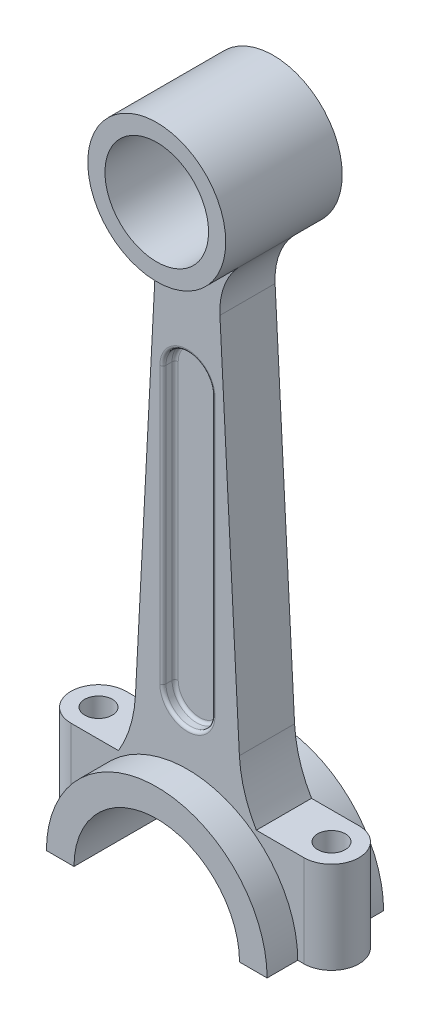
SolidWorks part; units mm, degrees
ref_plane "Front Plane" through (0, 0, 0) normal (0, 0, 1) x (1, 0, 0)
ref_plane "Top Plane" through (0, 0, 0) normal (0, 1, 0) x (1, 0, 0)
ref_plane "Right Plane" through (0, 0, 0) normal (1, 0, 0) x (0, 0, -1)
sketch "Sketch1" plane through (0, 0, 0) normal (0, 0, 1) x (1, 0, 0)
  line L0 (0, 0) -> (0, -201.2) construction
  line L1 (-10, -20.1556) -> (-17.8497, -169.9368)
  line L2 (10, -20.1556) -> (17.8497, -169.9368)
  line L3 (-36, -201.2) -> (36, -201.2) construction
  line L4 (-36, -201.2) -> (-27, -201.2)
  line L5 (27, -201.2) -> (36, -201.2)
  circle A0 centre (0, 0) radius 22.5
  circle A1 centre (0, 0) radius 16.9
  arc A2 (36, -201.2) -> (-36, -201.2) centre (0, -201.2) ccw
  arc A3 (27, -201.2) -> (-27, -201.2) centre (0, -201.2) ccw
  dimension "D1" = 45
  dimension "D2" = 33.8
  dimension "D3" = 72
  dimension "D4" = 54
  dimension "D5" = 201.2
  dimension "D6" = 20
  dimension "D7" = 6
extrude "Boss-Extrude1" add sketch "Sketch1" along normal mid plane 38 contours A1 A0 | A2 A3 region at (-11.5231, 18.5805, 0) region at (0, -166.005, 0)
extrude "Boss-Extrude2" add sketch "Sketch1<3>" along normal mid plane 18 contours L0 A0 L1 A2 | A0 L0 A2 L2 region at (7.1843, -100.8455, 0) region at (-7.1843, -100.8455, 0)
sketch "Sketch1<3>" plane through (0, 0, 0) normal (0, 0, 1) x (1, 0, 0) same geometry as "Sketch1"
sketch "Sketch2" plane through (0, 0, 9) normal (0, 0, 1) x (1, 0, 0)
  line L0 (0, 0) -> (0, -201.2) construction
  line L1 (0, -145.6) -> (0, -55.6) construction
  line L2 (-8, -145.6) -> (-8, -55.6)
  line L3 (8, -145.6) -> (8, -55.6)
  arc A0 (-8, -145.6) -> (8, -145.6) centre (0, -145.6) ccw
  arc A1 (8, -55.6) -> (-8, -55.6) centre (0, -55.6) ccw
  point P6 (0, -100.6)
  dimension "D2" = 8
  dimension "D1" = 90
extrude "Cut-Extrude1" cut sketch "Sketch2" against normal blind 4 contours A1 L2 A0 L3
mirror "Mirror1" about plane through (0, 0, 0) normal (0, 0, 1) of "Cut-Extrude1"
fillet "Fillet1" radius 1 16 edges at (0, -153.6, -5) (8, -100.6, -5) (0, -47.6, -5) (0, -153.6, -9) (8, -100.6, -9) (0, -47.6, -9) (0, -153.6, 5) (8, -100.6, 5) (0, -47.6, 5) (0, -153.6, 9) (8, -100.6, 9) (0, -47.6, 9) (-8, -100.6, -5) (-8, -100.6, -9) (-8, -100.6, 5) (-8, -100.6, 9)
fillet "Fillet2" radius 40 2 edges at (-17.8497, -169.9368, 0) (17.8497, -169.9368, 0)
fillet "Fillet3" radius 22.5 2 edges at (10, -20.1556, 0) (-10, -20.1556, 0)
ref_plane "Plane1" through (0, -171.2, 0) normal (0, -1, 0) x (-1, 0, 0)
sketch "Sketch3" plane through (0, -171.2, 0) normal (0, -1, 0) x (-1, 0, 0)
  line L0 (38, 0) -> (-38, 0) construction
  line L1 (38, -9) -> (-38, -9)
  line L2 (38, 9) -> (-38, 9)
  arc A0 (38, -9) -> (38, 9) centre (38, 0) ccw
  arc A1 (-38, 9) -> (-38, -9) centre (-38, 0) ccw
  point P2 (0, 0)
  dimension "D2" = 9
  dimension "D1" = 76
extrude "Boss-Extrude5" add sketch "Sketch3" along normal up to surface (30 mm away) contours A1 L1 A0 L2 up to face at (31.5, -201.2, 0)
sketch "Sketch6" plane through (0, 0, -9) normal (0, 0, -1) x (-1, 0, 0)
  line L0 (-27, -201.2) -> (27, -201.2) construction
  circle A0 centre (0, -201.2) radius 27
extrude "Cut-Extrude2" cut sketch "Sketch6" against normal blind 37
sketch "Sketch7" plane through (0, -171.2, 0) normal (0, -1, 0) x (-1, 0, 0)
  circle A0 centre (-38, 0) radius 4.5
  circle A1 centre (38, 0) radius 4.5
  dimension "D1" = 9
  dimension "D2" = 9
extrude "Cut-Extrude3" cut sketch "Sketch7" along normal blind 37
